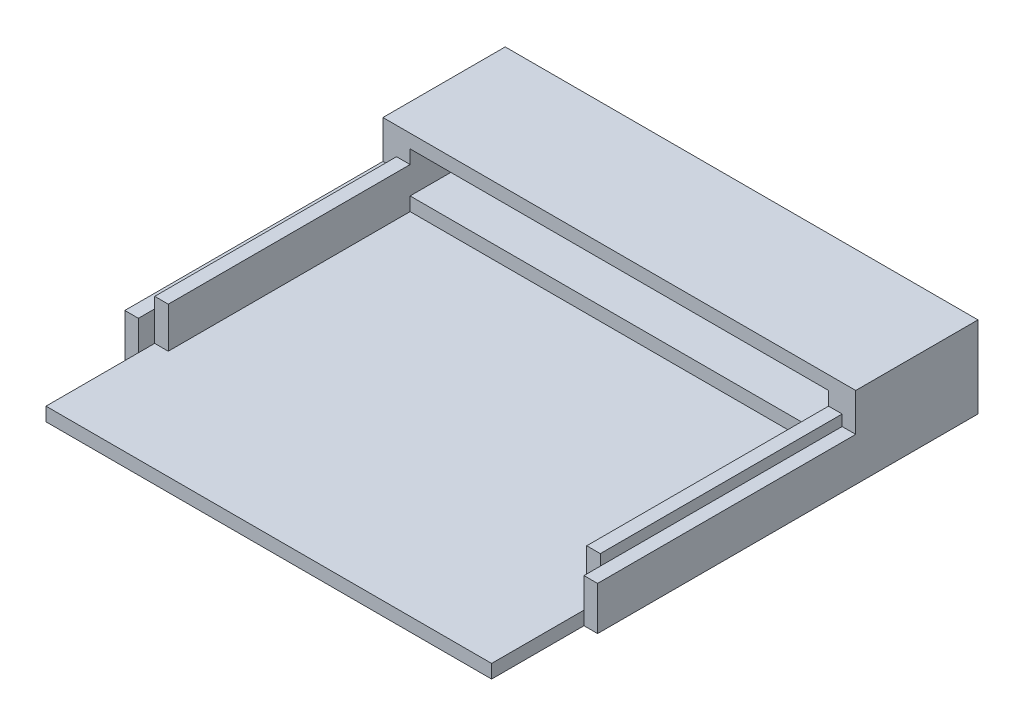
SolidWorks part; units mm, degrees
ref_plane "Front Plane" through (0, 0, 0) normal (0, 0, 1) x (1, 0, 0)
ref_plane "Top Plane" through (0, 0, 0) normal (0, 1, 0) x (1, 0, 0)
ref_plane "Right Plane" through (0, 0, 0) normal (1, 0, 0) x (0, 0, -1)
sketch "Sketch1" plane through (0, 0, 0) normal (0, 1, 0) x (1, 0, 0)
  line L0 (0, 0) -> (0, -5)
  line L2 (0, 0) -> (0, 84)
  line L3 (0, 84) -> (154, 84)
  line L4 (154, 0) -> (154, 84)
  line L5 (-5, -5) -> (159, -5)
  line L6 (-5, -5) -> (-5, 89)
  line L7 (-5, 89) -> (159, 89)
  line L8 (159, -5) -> (159, 89)
  line L9 (154, 0) -> (154, -5)
  dimension "D1" = 154
  dimension "D2" = 84
  dimension "D3" = 5
  dimension "D4" = 5
  dimension "D5" = 5
extrude "Boss-Extrude1" add sketch "Sketch1" against normal blind 5 contours L4 L3 L2 | L5 L8 L7 L6 L4 L2 L3 | L6 L5 L8 L7 region at (77, 0, -39.5) region at (-1.8903, 0, 2.5)
extrude "Boss-Extrude2" add sketch "Sketch1<3>" along normal blind 5 contours L4 L9 L5 L8 L7 L6 L0 L2 L3 region at (-1.8903, 0, 2.5)
sketch "Sketch1<3>" plane through (0, 0, 0) normal (0, 1, 0) x (1, 0, 0) same geometry as "Sketch1"
sketch "Sketch2" plane through (0, -5, 0) normal (0, -1, 0) x (-1, 0, 0)
  line L6 (5, -5) -> (-159, -5)
  line L7 (5, -5) -> (5, -35)
  line L8 (5, -35) -> (-159, -35)
  line L9 (-159, -5) -> (-159, -35)
  dimension "D1" = 30
extrude "Boss-Extrude3" add sketch "Sketch2" against normal blind 5
sketch "Sketch3" plane through (0, 5, 0) normal (0, 1, 0) x (1, 0, 0)
  line L2 (-5, 89) -> (-5, -5)
  line L4 (159, 89) -> (159, -5)
  line L7 (0, 89) -> (0, -5)
  line L9 (154, 89) -> (154, -5)
  line L13 (-5, -5) -> (-5, 89) construction
  line L14 (159, -5) -> (159, -35) construction
  line L15 (-5, 89) -> (159, 89) construction
  line L16 (-5, 89) -> (0, 89)
  line L17 (-5, -5) -> (0, -5)
  line L18 (154, -5) -> (159, -5)
  line L19 (159, 89) -> (154, 89)
  line L20 (-5, -35) -> (-5, -5) construction
  line L21 (-5, -5) -> (0, -5) construction
  point P4 (0, 0)
  point P5 (0, 0)
  point P11 (0, 0)
  point P12 (0, 0)
extrude "Boss-Extrude4" add sketch "Sketch3" along normal blind 10 contours L2 L17 L7 L16 | L4 L19 L9 L18 region at (-2.5, 5, -42) region at (156.5, 5, -42)
sketch "Sketch4" plane through (0, -5, 0) normal (0, -1, 0) x (1, 0, 0)
  line L1 (-5, -89) -> (-10, -89)
  line L2 (-5, -89) -> (-5, 11)
  line L3 (-5, 11) -> (-10, 11)
  line L4 (-10, -89) -> (-10, 11)
  line L5 (159, -89) -> (164, -89)
  line L6 (159, -89) -> (159, 11)
  line L7 (159, 11) -> (164, 11)
  line L8 (164, -89) -> (164, 11)
  dimension "D1" = 5
  dimension "D2" = 5
  dimension "D3" = 100
  dimension "D4" = 100
extrude "Boss-Extrude5" add sketch "Sketch4" against normal blind 16 contours L2 L1 L4 L3 | L6 L5 L8 L7
sketch "Sketch5" plane through (0, 15, 0) normal (0, 1, 0) x (1, 0, 0)
  line L0 (159, 89) -> (159, -5) construction
  line L1 (-5, 89) -> (0, 89)
  line L2 (-5, 89) -> (-5, 84)
  line L3 (-5, 84) -> (0, 84)
  line L4 (0, 89) -> (0, 84)
  line L5 (154, 89) -> (159, 89)
  line L6 (154, 89) -> (154, 84)
  line L7 (154, 84) -> (159, 84)
  line L8 (159, 89) -> (159, 84)
extrude "Cut-Extrude1" cut sketch "Sketch5" against normal up to surface (4 mm away) up to face at (-7, 11, -30.2)
sketch "Sketch6" plane through (0, 0, -89) normal (0, 0, -1) x (-1, 0, 0)
  line L1 (-164, 11) -> (10, 11)
  line L2 (-164, 11) -> (-164, -5)
  line L3 (-164, -5) -> (10, -5)
  line L4 (10, 11) -> (10, -5)
  line L5 (-154, 5) -> (0, 5)
  line L6 (-154, 5) -> (-154, 11)
  line L7 (-154, 11) -> (0, 11)
  line L8 (0, 5) -> (0, 11)
  line M1 (10, 11) -> (0, 11)
  line M2 (0, 11) -> (0, 5)
  line M3 (0, 5) -> (-154, 5)
  line M4 (-154, 5) -> (-154, 11)
  line M5 (-154, 11) -> (-164, 11)
  line M6 (-164, 11) -> (-164, -5)
  line M7 (-164, -5) -> (10, -5)
  line M8 (10, -5) -> (10, 11)
extrude "Boss-Extrude6" add sketch "Sketch6" along normal blind 40 contours M8 M1 M2 M3 M4 M5 M6 M7 region at (77, 0.5161, -89)
sketch "Sketch7" plane through (0, 0, 35) normal (0, 0, 1) x (1, 0, 0)
  line L1 (-5, 0) -> (159, 0)
  line L2 (-5, 0) -> (-5, -5)
  line L3 (-5, -5) -> (159, -5)
  line L4 (159, 0) -> (159, -5)
sketch "Sketch8" plane through (0, 0, -129) normal (0, 0, -1) x (-1, 0, 0)
  line L0 (-164, 11) -> (-154, 11)
  line L2 (-154, 11) -> (-154, 20)
  line L3 (-154, 20) -> (0, 20)
  line L4 (0, 11) -> (0, 20)
  line L6 (-164, 11) -> (-164, 25)
  line L7 (-164, 25) -> (10, 25)
  line L8 (10, 11) -> (10, 25)
  line L9 (10, 11) -> (0, 11)
  line L10 (10, -5) -> (10, 11) construction
  line L11 (0, 11) -> (0, 5) construction
  line L12 (-164, -5) -> (10, -5) construction
  dimension "D1" = 25
  dimension "D2" = 30
  dimension "D3" = 0
  dimension "D4" = 0
  dimension "D5" = 16
extrude "Boss-Extrude7" add sketch "Sketch8" against normal up to surface (45 mm away) up to face at (156.5, 13, -84)
sketch "Sketch9" plane through (0, 0, 35) normal (0, 0, 1) x (1, 0, 0)
  line L1 (-5, 0) -> (159, 0)
  line L2 (-5, 0) -> (-5, -5)
  line L3 (-5, -5) -> (159, -5)
  line L4 (159, 0) -> (159, -5)
extrude "Boss-Extrude8" add sketch "Sketch9" along normal blind 10
